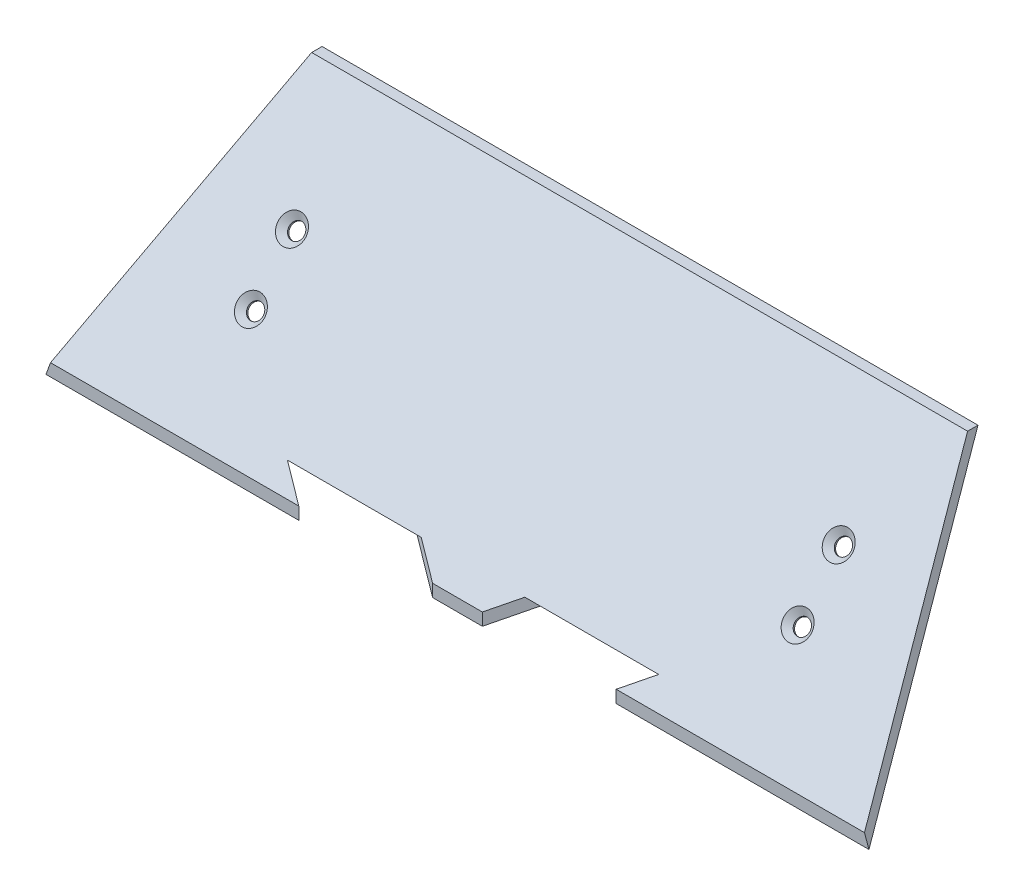
SolidWorks part; units mm, degrees
material "Delrin 2700 NC010, Low Viscosity Acetal Copolymer (SS)"
ref_plane "Front Plane" through (0, 0, 0) normal (0, 0, 1) x (1, 0, 0)
ref_plane "Top Plane" through (0, 0, 0) normal (0, 1, 0) x (1, 0, 0)
ref_plane "Right Plane" through (0, 0, 0) normal (1, 0, 0) x (0, 0, -1)
sketch "Sketch2" plane through (0, 0, 0) normal (1, 0, 0) x (0, 0, -1)
  line L0 (0, 0) -> (-2.3622, 0)
  line L1 (-2.3622, 0) -> (45.4805, 57.0167)
  line L2 (45.4805, 57.0167) -> (47.8427, 57.0167)
  line L3 (47.8427, 57.0167) -> (0, 0)
  dimension "D1" = 50
  dimension "D2" = 74.43
  dimension "D3" = 2.3622
extrude "Boss-Extrude1" add sketch "Sketch2" along normal blind 186.9479
sketch "Sketch3" plane through (0, 0, 0) normal (-1, 0, 0) x (0, 0, 1)
  line L0 (-4.1057, 4.893) -> (-4.1057, 7.7082)
  line L1 (-45.4805, 57.0167) -> (2.3622, 0) construction
  line L2 (-4.1057, 7.7082) -> (2.3622, 0)
  line L3 (2.3622, 0) -> (0, 0)
  line L4 (0, 0) -> (-4.1057, 4.893)
  line L5 (0, 0) -> (-47.8427, 57.0167) construction
  line L6 (-4.1057, 5.0046) -> (-4.1057, -12.9833) construction
extrude "Cut-Extrude1" cut sketch "Sketch3" against normal through all
sketch "Sketch4" plane through (93.4965, -1.9814, -4.1057) normal (0, 0, -1) x (-1, 0, 0)
  line L0 (93.4965, 58.998) -> (74.525, 58.998)
  line L1 (-93.4515, 58.998) -> (93.4965, 58.998) construction
  line L3 (74.525, 58.998) -> (93.4965, 6.8743)
  line L4 (93.4965, 6.8743) -> (93.4965, 58.998)
  line L5 (-93.4515, 6.8743) -> (-93.4515, 58.998)
  line L6 (-93.4515, 58.998) -> (-74.48, 58.998)
  line L7 (-74.48, 58.998) -> (-93.4515, 6.8743)
  dimension "D1" = 20
  dimension "D2" = 20
extrude "Cut-Extrude2" cut sketch "Sketch4" along normal through all
hole_wizard "CSK for M3 Flat Head Machine Screw1" positions "Sketch5" profile "Sketch6" countersink size "M3" standard "ANSI Metric"
sketch "Sketch5" plane through (0, 1.1632, 1.3862) normal (0, 0.6428, 0.766) x (1, 0, 0)
  point P0 (31.3777, 46.6549)
  point P2 (31.3777, 32.1455)
sketch "Sketch6" plane through (31.3777, 36.9029, -28.603) normal (1, 0, 0) x (0, -0.766, 0.6428)
  line L0 (0, 0) -> (0, 5)
  line L1 (0, 5) -> (1.75, 5)
  line L2 (1.75, 5) -> (1.75, 1.4)
  line L3 (1.75, 1.4) -> (3.15, 0)
  line L5 (3.15, 0) -> (0, 0)
  line L6 (-1.75, 1.4) -> (-3.15, 0) construction
  line L10 (0, 5) -> (-1.75, 5) construction
  line L11 (0, -6.35) -> (0, 107.95) construction
  dimension "Hole Dia." = 3.5
  dimension "Hole Depth" = 5
  dimension "Near C'Sink Dia." = 6.3
  dimension "Near C'Sink Angle" = 90
  dimension "Drill Angle" = 180
ref_plane "Plane1" through (93.474, 0, 0) normal (1, 0, 0) x (0, 0, -1)
mirror "Mirror1" about plane through (93.474, 0, 0) normal (1, 0, 0) of "CSK for M3 Flat Head Machine Screw1"
ref_plane "Plane2" through (112.633, 0, -65.0287) normal (-0.866, 0, 0.5) x (0.5, 0, 0.866)
sketch "Sketch7" plane through (112.633, 0, -65.0287) normal (-0.866, 0, 0.5) x (0.5, 0, 0.866)
  line L0 (46.0064, 4.9186) -> (46.0064, 3.9186)
  line L1 (61.2064, 11.9186) -> (46.0064, 11.9186)
  line L2 (61.2064, 11.9186) -> (61.2064, 4.9186)
  line L3 (61.2064, 4.9186) -> (46.0064, 4.9186)
  line L4 (46.0064, 11.9186) -> (46.0064, 4.9186)
  line L5 (46.0064, 3.9186) -> (61.2064, 3.9186)
  line L6 (61.2064, 3.9186) -> (61.2064, 4.9186)
  dimension "D1" = 1
extrude "Cut-Extrude3" cut sketch "Sketch7" along normal up to surface (8.7674 mm away) contours L1 L4 L3 L2 | L5 L6 L3 L0 region at (139.4362, 4.4186, -18.6042) region at (139.4362, 8.4186, -18.6042) up to face at (155.5703, 34.4899, -26.5782)
mirror "Mirror2" about plane through (93.474, 0, 0) normal (1, 0, 0) of "Cut-Extrude3"
